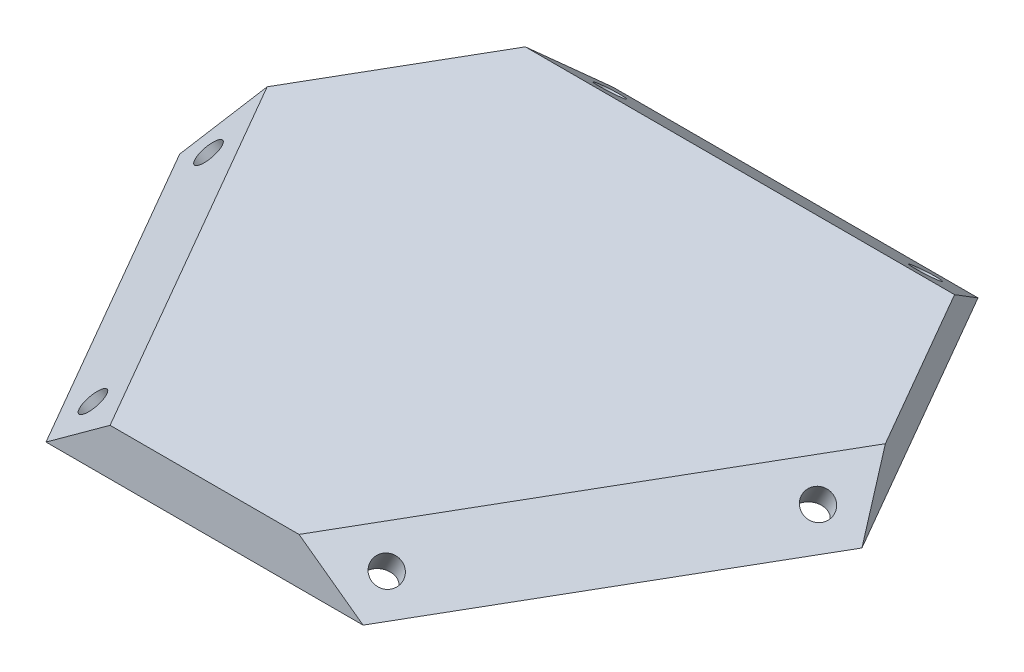
SolidWorks part; units mm, degrees
ref_plane "Front Plane" through (0, 0, 0) normal (0, 0, 1) x (1, 0, 0)
ref_plane "Top Plane" through (0, 0, 0) normal (0, 1, 0) x (1, 0, 0)
ref_plane "Right Plane" through (0, 0, 0) normal (1, 0, 0) x (0, 0, -1)
sketch "Sketch1" plane through (0, 0, 0) normal (0, 1, 0) x (1, 0, 0)
  line L7 (-60, 0) -> (-30, -51.9615)
  line L8 (-30, -51.9615) -> (30, -51.9615)
  line L9 (30, -51.9615) -> (60, 0)
  line L10 (60, 0) -> (30, 51.9615)
  line L11 (30, 51.9615) -> (-30, 51.9615)
  line L12 (-30, 51.9615) -> (-60, 0)
  circle A1 centre (0, 0) radius 51.9615 construction
  dimension "D1" = 60
extrude "Boss-Extrude1" add sketch "Sketch1" along normal blind 8
chamfer "Chamfer1" distance 10 angle 50 3 edges at (0, 8, -51.9615) (-45, 8, 25.9808) (45, 8, 25.9808) first distance on face at (0, 4, -51.9615) first distance on face at (-45, 4, 25.9808) first distance on face at (45, 4, 25.9808)
sketch "Sketch4" plane through (17.74, 24.4124, 10.2422) normal (0.5567, 0.766, 0.3214) x (0.8301, -0.4979, -0.251)
  line L0 (46.1828, 6.3514) -> (3.0135, -46.52) construction
  line L1 (9.5744, -48.3238) -> (-3.5474, -44.7162) construction
  line L2 (43.1032, 12.419) -> (49.2624, 0.2838) construction
  circle A0 centre (41.7556, 0.9292) radius 2.3
  circle A1 centre (7.4407, -41.0978) radius 2.3
  dimension "D1" = 4.6
  dimension "D2" = 7
  dimension "D3" = 7
sketch "Sketch6" plane through (-17.74, 24.4124, 10.2422) normal (-0.5567, 0.766, 0.3214) x (0.8307, 0.5133, 0.2154)
  line L0 (-45.9011, 8.1412) -> (-4.8189, -46.3678) construction
  line L1 (1.8071, -44.8203) -> (-11.445, -47.9153) construction
  line L2 (-49.2141, 2.1979) -> (-42.5881, 14.0846) construction
  circle A0 centre (-41.688, 2.5511) radius 2.3
  circle A1 centre (-9.0321, -40.7777) radius 2.3
  dimension "D1" = 4.6
  dimension "D2" = 7
  dimension "D3" = 7
sketch "Sketch7" plane through (0, 24.4124, -20.4844) normal (0, 0.766, -0.6428) x (1, 0, 0)
  line L0 (34.1284, 31.7561) -> (-34.1284, 31.7561) construction
  line L1 (-36.8806, 25.5332) -> (-31.3761, 37.979) construction
  line L2 (31.3761, 37.979) -> (36.8806, 25.5332) construction
  circle A0 centre (-27.1284, 31.7561) radius 2.3
  circle A1 centre (27.1284, 31.7561) radius 2.3
  dimension "D1" = 4.6
  dimension "D2" = 7
  dimension "D3" = 7
extrude "Cut-Extrude1" cut sketch "Sketch4" against normal through all
extrude "Cut-Extrude2" cut sketch "Sketch7" against normal through all
extrude "Cut-Extrude3" cut sketch "Sketch6" against normal through all
equation "\"`9\"=8"
